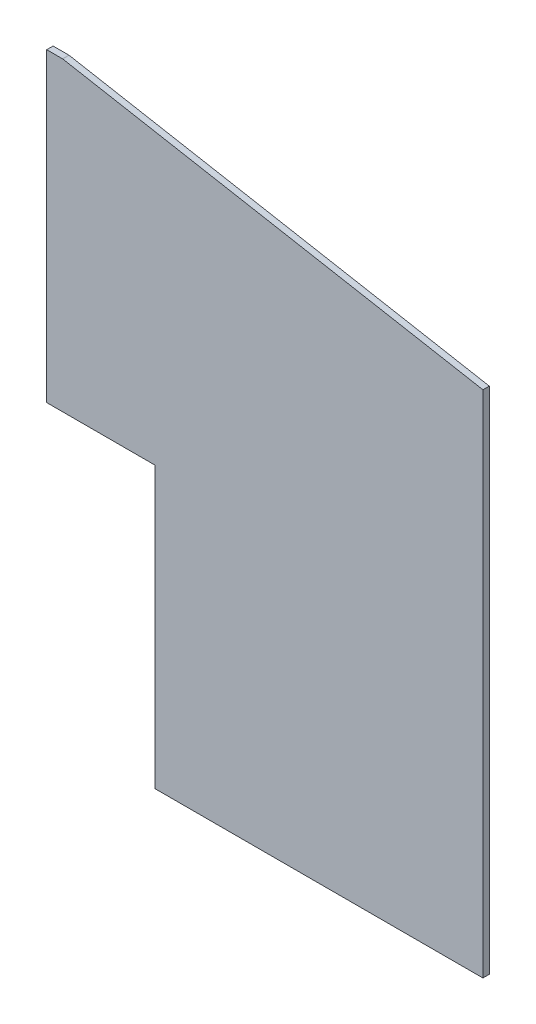
SolidWorks part; units mm, degrees
material "Hardox"
ref_plane "Ön Düzlem" through (0, 0, 0) normal (0, 0, 1) x (1, 0, 0)
ref_plane "Üst Düzlem" through (0, 0, 0) normal (0, 1, 0) x (1, 0, 0)
ref_plane "Sağ Düzlem" through (0, 0, 0) normal (1, 0, 0) x (0, 0, -1)
sketch "Çizim1" plane through (0, 0, 0) normal (0, 0, 1) x (1, 0, 0)
  line L0 (0, 0) -> (0, 800)
  line L1 (0, 800) -> (660, 920)
  line L2 (660, 920) -> (1840, 920)
  line L3 (1840, 920) -> (2500, 800)
  line L4 (2500, 800) -> (2500, 0)
  line L5 (2500, 0) -> (0, 0)
  dimension "D1" = 660
  dimension "D2" = 120
  dimension "D3" = 800
  dimension "D4" = 2500
base flange "Taban-Flanş1" sketch "Çizim1" thickness 10 reverse thickness direction no parameters "D1"=5
sketch "Çizim2" plane through (0, 0, 0) normal (0, 0, 1) x (1, 0, 0)
  line L0 (2500, 0) -> (2500, 800) construction
  line L1 (0, 0) -> (1985, 0)
  line L2 (0, 0) -> (0, 440)
  line L3 (0, 440) -> (1985, 440)
  line L4 (1985, 0) -> (1985, 440)
  dimension "D1" = 1985
  dimension "D2" = 440
  dimension "D3" = 515
extrude "Kes-Ekstrüzyon1" cut sketch "Çizim2" against normal through all both and the other way through all
sketch "Çizim3" plane through (0, 0, 0) normal (0, 0, 1) x (1, 0, 0)
  line L0 (1830, 440) -> (1830, 920)
  line L1 (0, 440) -> (1985, 440) construction
  line L2 (1840, 920) -> (660, 920) construction
  line L3 (0, 800) -> (0, 440) construction
  line L4 (1830, 920) -> (2119.8993, 1128.4051)
  line L5 (2119.8993, 1128.4051) -> (3042.604, 783.7804)
  line L6 (3042.604, 783.7804) -> (2495.0955, -369.6005)
  line L7 (2495.0955, -369.6005) -> (1733.5862, -191.7297)
  line L8 (1733.5862, -191.7297) -> (1830, 440)
  dimension "D1" = 1830
sketch "Çizim4" plane through (0, 0, 0) normal (0, 0, 1) x (1, 0, 0)
  line L0 (0, 800) -> (0, 440) construction
  line L1 (1813, 1304.0739) -> (-329.3531, 1304.0739)
  line L2 (1813, 1304.0739) -> (1813, 244.8736)
  line L3 (1813, 244.8736) -> (-329.3531, 244.8736)
  line L4 (-329.3531, 1304.0739) -> (-329.3531, 244.8736)
  line L5 (1985, 440) -> (1985, 0) construction
  dimension "D1" = 1813
  dimension "D2" = 172
extrude "Kes-Ekstrüzyon2" cut sketch "Çizim4" against normal through all both and the other way through all
sketch "Çizim5" plane through (0, 0, 0) normal (0, 0, 1) x (1, 0, 0)
  line L0 (1985, 440) -> (1985, 0) construction
  line L1 (1624.3407, 979.8371) -> (1815, 979.8371)
  line L2 (1624.3407, 979.8371) -> (1624.3407, 380.9712)
  line L3 (1624.3407, 380.9712) -> (1815, 380.9712)
  line L4 (1815, 979.8371) -> (1815, 380.9712)
  dimension "D1" = 170
extrude "Kes-Ekstrüzyon3" cut sketch "Çizim5" against normal through all both and the other way through all
sketch "Çizim6" plane through (0, 0, 0) normal (0, 0, 1) x (1, 0, 0)
  line L0 (1815, 460) -> (2500, 460)
  line L1 (1815, 920) -> (1815, 440) construction
  line L2 (2500, 0) -> (2500, 800) construction
  line L3 (1985, 0) -> (2500, 0) construction
  line L4 (1815, 440) -> (1985, 440) construction
  line L5 (1985, 440) -> (1985, 0) construction
  dimension "D1" = 460
  dimension "D2" = 20
  dimension "D3" = 170
  dimension "D4" = 515
sketch "Büküm-Çizgileri1" [suppressed] plane through (0, 0, 0) normal (0, 1, 0) x (1, 0, 0)
sketch "Sınırlandırma-Kutusu1" [suppressed] plane through (0, 0, 0) normal (0, 1, 0) x (1, 0, 0)
sheet metal parameters "Sac-Levha1" thickness 10 parameters "D1"=5
flat pattern "Düz-Çoğaltma1" [suppressed]
sketch "Büküm-Çizgileri2" plane through (0, 0, 0) normal (0, 1, 0) x (1, 0, 0)
sketch3d "Sınırlandırma-Kutusu2" [suppressed]
  line L0 (0, 0, 0) -> (-2500, 0, 0) construction
  line L1 (0, 920, 0) -> (-2500, 920, 0) construction
  line L2 (0, 0, 0) -> (0, 920, 0) construction
  line L3 (-2500, 0, 0) -> (-2500, 920, 0) construction
sheet metal parameters "Sac-Levha2" thickness 10 parameters "D1"=5
flat pattern "Düz-Çoğaltma1"
sketch "Büküm-Çizgileri2" plane through (0, 0, 0) normal (0, 1, 0) x (1, 0, 0)
sketch3d "Sınırlandırma-Kutusu2" [suppressed]
  line L0 (80, 1240, 0) -> (2640.8, 774.4, 0) construction
  line L1 (-77.28, 374.96, 0) -> (2483.52, -90.64, 0) construction
  line L2 (80, 1240, 0) -> (-77.28, 374.96, 0) construction
  line L3 (2640.8, 774.4, 0) -> (2483.52, -90.64, 0) construction
sheet metal parameters "Sac-Levha4" thickness 10 parameters "D1"=5
flat pattern "Düz-Çoğaltma1"
sketch "Büküm-Çizgileri2" plane through (0, 0, 0) normal (0, 1, 0) x (1, 0, 0)
sketch3d "Sınırlandırma-Kutusu2" [suppressed]
  line L0 (2500, 920, 0) -> (2500, 0, 0) construction
  line L1 (1813, 920, 0) -> (1813, 0, 0) construction
  line L2 (2500, 920, 0) -> (1813, 920, 0) construction
  line L3 (2500, 0, 0) -> (1813, 0, 0) construction
sheet metal parameters "Sac-Levha5" thickness 10 parameters "D1"=5
flat pattern "Düz-Çoğaltma1"
sketch "Büküm-Çizgileri2" plane through (0, 0, 0) normal (0, 1, 0) x (1, 0, 0)
sketch3d "Sınırlandırma-Kutusu2" [suppressed]
  line L0 (2500, 920, 0) -> (2500, 0, 0) construction
  line L1 (1815, 920, 0) -> (1815, 0, 0) construction
  line L2 (2500, 920, 0) -> (1815, 920, 0) construction
  line L3 (2500, 0, 0) -> (1815, 0, 0) construction
